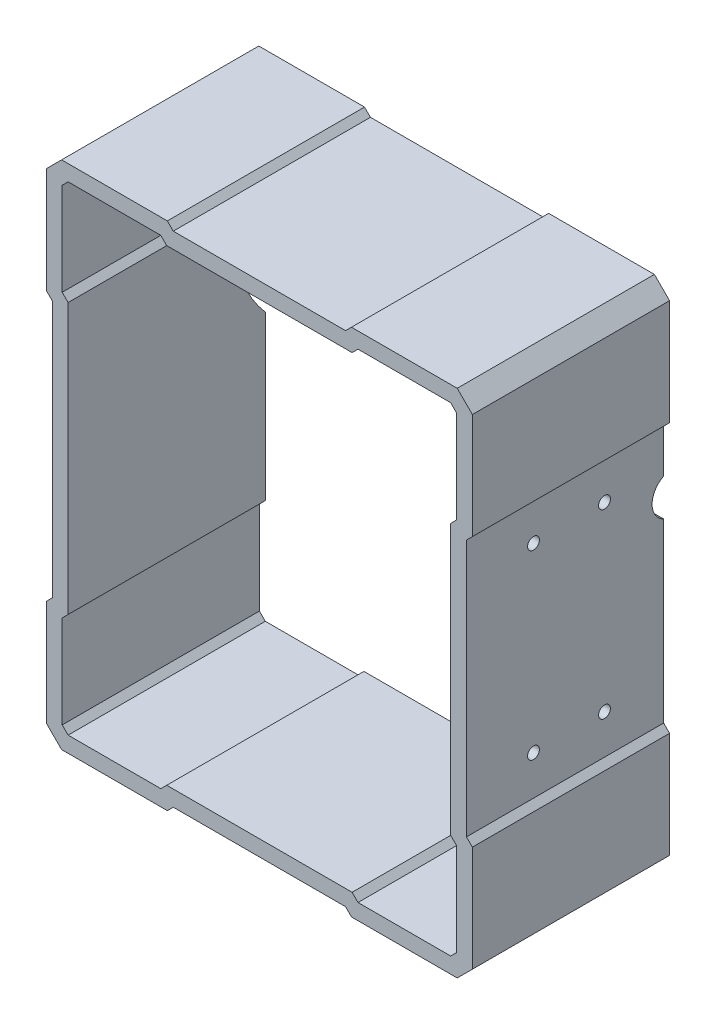
SolidWorks part; units mm, degrees
ref_plane "Front" through (0, 0, 0) normal (0, 0, 1) x (1, 0, 0)
ref_plane "Top" through (0, 0, 0) normal (0, 1, 0) x (1, 0, 0)
ref_plane "Right" through (0, 0, 0) normal (1, 0, 0) x (0, 0, -1)
sketch "草图1" plane through (0, 0, 0) normal (0, 0, 1) x (1, 0, 0)
  line L0 (25, 71.5) -> (23.5, 70) construction
  line L1 (23.5, 65.5) -> (25, 65.5) construction
  line L2 (25, 65.5) -> (43.5, 65.5) construction
  line L3 (43.5, 65.5) -> (43.5, 46.5) construction
  line L4 (50, 46.5) -> (50, 70) construction
  line L5 (50, 70) -> (48.5, 71.5) construction
  line L6 (48.5, 71.5) -> (25, 71.5) construction
  line L7 (23.5, 70) -> (-23.5, 70) construction
  line L8 (-23.5, 65.5) -> (23.5, 65.5) construction
  line L9 (-23.5, 70) -> (-25, 71.5) construction
  line L10 (-25, 65.5) -> (-23.5, 65.5) construction
  line L11 (-48.5, 71.5) -> (-50, 70) construction
  line L12 (-50, 70) -> (-50, 46.5) construction
  line L13 (-43.5, 46.5) -> (-43.5, 65.5) construction
  line L14 (-43.5, 65.5) -> (-25, 65.5) construction
  line L15 (-25, 71.5) -> (-48.5, 71.5) construction
  line L16 (-43.5, -23.5) -> (-43.5, -2.7997) construction
  line L17 (-43.5, 2.7997) -> (-43.5, 45) construction
  line L18 (-48.5, 45) -> (-48.5, -23.5) construction
  line L19 (-50, 46.5) -> (-48.5, 45) construction
  line L20 (-43.5, 45) -> (-43.5, 46.5) construction
  line L21 (-48.5, -23.5) -> (-50, -25) construction
  line L22 (-43.5, -25) -> (-43.5, -23.5) construction
  line L23 (-50, -25) -> (-50, -31.8) construction
  line L24 (-50, -31.8) -> (-43.5, -31.8) construction
  line L25 (-43.5, -31.8) -> (-43.5, -25) construction
  line L26 (-50, -31.8) -> (-50, -38.2) construction
  line L27 (-50, -38.2) -> (-43.5, -38.2) construction
  line L28 (-43.5, -38.2) -> (-43.5, -31.8) construction
  line L29 (-43.5, -31.8) -> (-50, -31.8) construction
  line L30 (-50, -48.5) -> (-48.5, -50) construction
  line L31 (-48.5, -50) -> (-38.2, -50) construction
  line L32 (-38.2, -50) -> (-38.2, -43.1) construction
  line L33 (-38.2, -43.1) -> (-43.5, -43.1) construction
  line L34 (-43.5, -43.1) -> (-43.5, -38.2) construction
  line L35 (-43.5, -38.2) -> (-50, -38.2) construction
  line L36 (-50, -38.2) -> (-50, -48.5) construction
  line L37 (-38.2, -50) -> (-31.8, -50) construction
  line L38 (-31.8, -50) -> (-31.8, -43.1) construction
  line L39 (-31.8, -43.1) -> (-38.2, -43.1) construction
  line L40 (-38.2, -43.1) -> (-38.2, -50) construction
  line L41 (-25, -43.1) -> (-31.8, -43.1) construction
  line L42 (-31.8, -43.1) -> (-31.8, -50) construction
  line L43 (-31.8, -50) -> (-25, -50) construction
  line L44 (-25, -50) -> (-23.5, -48.5) construction
  line L45 (-23.5, -43.1) -> (-25, -43.1) construction
  line L46 (23.5, -48.5) -> (25, -50) construction
  line L47 (25, -43.1) -> (23.5, -43.1) construction
  line L48 (23.5, -43.1) -> (6.5175, -43.1) construction
  line L49 (-6.5175, -43.1) -> (-23.5, -43.1) construction
  line L50 (-23.5, -48.5) -> (23.5, -48.5) construction
  line L51 (25, -50) -> (31.8, -50) construction
  line L52 (31.8, -50) -> (31.8, -43.1) construction
  line L53 (31.8, -43.1) -> (25, -43.1) construction
  line L54 (31.8, -50) -> (38.2, -50) construction
  line L55 (38.2, -50) -> (38.2, -43.1) construction
  line L56 (38.2, -43.1) -> (31.8, -43.1) construction
  line L57 (31.8, -43.1) -> (31.8, -50) construction
  line L58 (43.5, -38.2) -> (43.5, -43.1) construction
  line L59 (43.5, -43.1) -> (38.2, -43.1) construction
  line L60 (38.2, -43.1) -> (38.2, -50) construction
  line L61 (38.2, -50) -> (48.5, -50) construction
  line L62 (48.5, -50) -> (50, -48.5) construction
  line L63 (50, -48.5) -> (50, -38.2) construction
  line L64 (50, -38.2) -> (43.5, -38.2) construction
  line L65 (50, -38.2) -> (50, -31.8) construction
  line L66 (50, -31.8) -> (43.5, -31.8) construction
  line L67 (43.5, -31.8) -> (43.5, -38.2) construction
  line L68 (43.5, -38.2) -> (50, -38.2) construction
  line L69 (43.5, -25) -> (43.5, -31.8) construction
  line L70 (43.5, -31.8) -> (50, -31.8) construction
  line L71 (50, -31.8) -> (50, -25) construction
  line L72 (43.5, -23.5) -> (43.5, -25) construction
  line L73 (50, -25) -> (48.5, -23.5) construction
  line L74 (43.5, 46.5) -> (43.5, 45) construction
  line L75 (48.5, 45) -> (50, 46.5) construction
  line L76 (43.5, 45) -> (43.5, 2.7997) construction
  line L77 (43.5, -2.7997) -> (43.5, -23.5) construction
  line L78 (48.5, -23.5) -> (48.5, 45) construction
  line L79 (25, 71.5) -> (23.5, 70)
  line L80 (23.5, 65.5) -> (25, 65.5) construction
  line L81 (25, 65.5) -> (43.5, 65.5) construction
  line L82 (43.5, 65.5) -> (43.5, 46.5) construction
  line L83 (50, 46.5) -> (50, 70)
  line L84 (50, 70) -> (48.5, 71.5)
  line L85 (48.5, 71.5) -> (25, 71.5)
  line L86 (23.5, 70) -> (-23.5, 70)
  line L87 (-23.5, 65.5) -> (23.5, 65.5) construction
  line L88 (-23.5, 70) -> (-25, 71.5)
  line L89 (-25, 65.5) -> (-23.5, 65.5) construction
  line L90 (-48.5, 71.5) -> (-50, 70)
  line L91 (-50, 70) -> (-50, 46.5)
  line L92 (-43.5, 46.5) -> (-43.5, 65.5) construction
  line L93 (-43.5, 65.5) -> (-25, 65.5) construction
  line L94 (-25, 71.5) -> (-48.5, 71.5)
  line L95 (-43.5, -23.5) -> (-43.5, -2.7997) construction
  line L96 (-43.5, 2.7997) -> (-43.5, 45) construction
  line L97 (-48.5, 45) -> (-48.5, -23.5)
  line L98 (-50, 46.5) -> (-48.5, 45)
  line L99 (-43.5, 45) -> (-43.5, 46.5) construction
  line L100 (-48.5, -23.5) -> (-50, -25)
  line L101 (-43.5, -25) -> (-43.5, -23.5) construction
  line L102 (-50, -25) -> (-50, -31.8)
  line L103 (-50, -31.8) -> (-43.5, -31.8) construction
  line L104 (-43.5, -31.8) -> (-43.5, -25) construction
  line L105 (-50, -31.8) -> (-50, -38.2)
  line L106 (-50, -38.2) -> (-43.5, -38.2) construction
  line L107 (-43.5, -38.2) -> (-43.5, -31.8) construction
  line L108 (-43.5, -31.8) -> (-50, -31.8) construction
  line L109 (-50, -48.5) -> (-48.5, -50)
  line L110 (-48.5, -50) -> (-38.2, -50)
  line L111 (-38.2, -50) -> (-38.2, -43.1) construction
  line L112 (-38.2, -43.1) -> (-43.5, -43.1) construction
  line L113 (-43.5, -43.1) -> (-43.5, -38.2) construction
  line L114 (-43.5, -38.2) -> (-50, -38.2) construction
  line L115 (-50, -38.2) -> (-50, -48.5)
  line L116 (-38.2, -50) -> (-31.8, -50)
  line L117 (-31.8, -50) -> (-31.8, -43.1) construction
  line L118 (-31.8, -43.1) -> (-38.2, -43.1) construction
  line L119 (-38.2, -43.1) -> (-38.2, -50) construction
  line L120 (-25, -43.1) -> (-31.8, -43.1) construction
  line L121 (-31.8, -43.1) -> (-31.8, -50) construction
  line L122 (-31.8, -50) -> (-25, -50)
  line L123 (-25, -50) -> (-23.5, -48.5)
  line L124 (-23.5, -43.1) -> (-25, -43.1) construction
  line L125 (23.5, -48.5) -> (25, -50)
  line L126 (25, -43.1) -> (23.5, -43.1) construction
  line L127 (23.5, -43.1) -> (6.5175, -43.1) construction
  line L128 (-6.5175, -43.1) -> (-23.5, -43.1) construction
  line L129 (-23.5, -48.5) -> (23.5, -48.5)
  line L130 (25, -50) -> (31.8, -50)
  line L131 (31.8, -50) -> (31.8, -43.1) construction
  line L132 (31.8, -43.1) -> (25, -43.1) construction
  line L133 (31.8, -50) -> (38.2, -50)
  line L134 (38.2, -50) -> (38.2, -43.1) construction
  line L135 (38.2, -43.1) -> (31.8, -43.1) construction
  line L136 (31.8, -43.1) -> (31.8, -50) construction
  line L137 (43.5, -38.2) -> (43.5, -43.1) construction
  line L138 (43.5, -43.1) -> (38.2, -43.1) construction
  line L139 (38.2, -43.1) -> (38.2, -50) construction
  line L140 (38.2, -50) -> (48.5, -50)
  line L141 (48.5, -50) -> (50, -48.5)
  line L142 (50, -48.5) -> (50, -38.2)
  line L143 (50, -38.2) -> (43.5, -38.2) construction
  line L144 (50, -38.2) -> (50, -31.8)
  line L145 (50, -31.8) -> (43.5, -31.8) construction
  line L146 (43.5, -31.8) -> (43.5, -38.2) construction
  line L147 (43.5, -38.2) -> (50, -38.2) construction
  line L148 (43.5, -25) -> (43.5, -31.8) construction
  line L149 (43.5, -31.8) -> (50, -31.8) construction
  line L150 (50, -31.8) -> (50, -25)
  line L151 (43.5, -23.5) -> (43.5, -25) construction
  line L152 (50, -25) -> (48.5, -23.5)
  line L153 (43.5, 46.5) -> (43.5, 45) construction
  line L154 (48.5, 45) -> (50, 46.5)
  line L155 (43.5, 45) -> (43.5, 2.7997) construction
  line L156 (43.5, -2.7997) -> (43.5, -23.5) construction
  line L157 (48.5, -23.5) -> (48.5, 45)
  line L158 (54, -31.8) -> (54, -23.3431)
  line L159 (54, -23.3431) -> (52.5, -21.8431)
  line L160 (52.5, -21.8431) -> (52.5, 43.3431)
  line L161 (52.5, 43.3431) -> (54, 44.8431)
  line L162 (54, 44.8431) -> (54, 71.6569)
  line L163 (54, 71.6569) -> (50.1569, 75.5)
  line L164 (50.1569, 75.5) -> (23.3431, 75.5)
  line L165 (23.3431, 75.5) -> (21.8431, 74)
  line L166 (21.8431, 74) -> (-21.8431, 74)
  line L167 (-21.8431, 74) -> (-23.3431, 75.5)
  line L168 (-23.3431, 75.5) -> (-50.1569, 75.5)
  line L169 (-50.1569, 75.5) -> (-54, 71.6569)
  line L170 (-54, 71.6569) -> (-54, 44.8431)
  line L171 (-54, 44.8431) -> (-52.5, 43.3431)
  line L172 (-52.5, 43.3431) -> (-52.5, -21.8431)
  line L173 (-52.5, -21.8431) -> (-54, -23.3431)
  line L174 (-54, -23.3431) -> (-54, -31.8)
  line L175 (54, -38.2) -> (54, -31.8)
  line L176 (38.2, -54) -> (50.1569, -54)
  line L177 (50.1569, -54) -> (54, -50.1569)
  line L178 (54, -50.1569) -> (54, -38.2)
  line L179 (31.8, -54) -> (38.2, -54)
  line L180 (-31.8, -54) -> (-23.3431, -54)
  line L181 (-23.3431, -54) -> (-21.8431, -52.5)
  line L182 (-21.8431, -52.5) -> (21.8431, -52.5)
  line L183 (21.8431, -52.5) -> (23.3431, -54)
  line L184 (23.3431, -54) -> (31.8, -54)
  line L185 (-38.2, -54) -> (-31.8, -54)
  line L186 (-54, -38.2) -> (-54, -50.1569)
  line L187 (-54, -50.1569) -> (-50.1569, -54)
  line L188 (-50.1569, -54) -> (-38.2, -54)
  line L189 (-54, -31.8) -> (-54, -38.2)
  arc A0 (-43.5, 2.7997) -> (-43.5, -2.7997) centre (0, 0) ccw construction
  arc A1 (-6.5175, -43.1) -> (6.5175, -43.1) centre (0, 0) ccw construction
  arc A2 (43.5, -2.7997) -> (43.5, 2.7997) centre (0, 0) ccw construction
  arc A3 (-43.5, 2.7997) -> (-43.5, -2.7997) centre (0, 0) ccw construction
  arc A4 (-6.5175, -43.1) -> (6.5175, -43.1) centre (0, 0) ccw construction
  arc A5 (43.5, -2.7997) -> (43.5, 2.7997) centre (0, 0) ccw construction
  dimension "D1" = 4
extrude "凸台-拉伸1" add sketch "草图1" along normal mid plane 20
sketch "草图2" plane through (-52.5, 0, 0) normal (-1, 0, 0) x (0, 0, 1)
  line L0 (-10, 43.3431) -> (-10, -21.8431) construction
  line L1 (-10, 43.3431) -> (-10, 17.8909)
  line L2 (-10, 71.6569) -> (-10, 44.8431) construction
  line L3 (-10, 62.1091) -> (-10, 44.8431)
  line L4 (-10, 43.3431) -> (-10, 44.8431)
  arc A0 (-1.7971, 38.2166) -> (-1.7971, 41.7834) centre (-35.5, 40) ccw construction
  arc A1 (-17.1041, 11.7042) -> (-1.7971, 38.2166) centre (-35.5, 40) ccw construction
  arc A2 (-1.7971, 41.7834) -> (-17.1041, 68.2958) centre (-35.5, 40) ccw construction
  arc A3 (-1.7971, 38.2166) -> (-1.7971, 41.7834) centre (-35.5, 40) ccw
  arc A4 (-10, 17.8909) -> (-1.7971, 38.2166) centre (-35.5, 40) ccw
  arc A5 (-1.7971, 41.7834) -> (-10, 62.1091) centre (-35.5, 40) ccw
extrude "切除-拉伸1" cut sketch "草图2" along normal mid plane 10
sketch "草图3" plane through (52.5, 0, 0) normal (1, 0, 0) x (0, 0, -1)
  line L0 (10, -21.8431) -> (10, 43.3431) construction
  line L1 (10, 22.9681) -> (10, 32.3847)
  arc A0 (13.1086, 32.8672) -> (17.0655, 25.4253) centre (12.3226, 27.6764) ccw construction
  arc A1 (10, 32.3847) -> (10, 22.9681) centre (12.3226, 27.6764) ccw
extrude "切除-拉伸2" cut sketch "草图3" against normal blind 20 contours A1 L1
sketch "草图4" plane through (0, 0, 10) normal (0, 0, 1) x (1, 0, 0)
  line L24 (54, -50.1569) -> (54, -23.3431)
  line L25 (54, -23.3431) -> (52.5, -21.8431)
  line L26 (52.5, -21.8431) -> (52.5, 43.3431)
  line L27 (52.5, 43.3431) -> (54, 44.8431)
  line L28 (54, 44.8431) -> (54, 71.6569)
  line L29 (54, 71.6569) -> (50.1569, 75.5)
  line L30 (50.1569, 75.5) -> (23.3431, 75.5)
  line L31 (23.3431, 75.5) -> (21.8431, 74)
  line L32 (21.8431, 74) -> (-21.8431, 74)
  line L33 (-21.8431, 74) -> (-23.3431, 75.5)
  line L34 (-23.3431, 75.5) -> (-50.1569, 75.5)
  line L35 (-50.1569, 75.5) -> (-54, 71.6569)
  line L36 (-54, 71.6569) -> (-54, 44.8431)
  line L37 (-54, 44.8431) -> (-52.5, 43.3431)
  line L38 (-52.5, 43.3431) -> (-52.5, -21.8431)
  line L39 (-52.5, -21.8431) -> (-54, -23.3431)
  line L40 (-54, -23.3431) -> (-54, -50.1569)
  line L41 (-54, -50.1569) -> (-50.1569, -54)
  line L42 (-50.1569, -54) -> (-23.3431, -54)
  line L43 (-23.3431, -54) -> (-21.8431, -52.5)
  line L44 (-21.8431, -52.5) -> (21.8431, -52.5)
  line L45 (21.8431, -52.5) -> (23.3431, -54)
  line L46 (23.3431, -54) -> (50.1569, -54)
  line L47 (50.1569, -54) -> (54, -50.1569)
  line L48 (54, -50.1569) -> (54, -23.3431)
  line L49 (54, -23.3431) -> (52.5, -21.8431)
  line L50 (52.5, -21.8431) -> (52.5, 43.3431)
  line L51 (52.5, 43.3431) -> (54, 44.8431)
  line L52 (54, 44.8431) -> (54, 71.6569)
  line L53 (54, 71.6569) -> (50.1569, 75.5)
  line L54 (50.1569, 75.5) -> (23.3431, 75.5)
  line L55 (23.3431, 75.5) -> (21.8431, 74)
  line L56 (21.8431, 74) -> (-21.8431, 74)
  line L57 (-21.8431, 74) -> (-23.3431, 75.5)
  line L58 (-23.3431, 75.5) -> (-50.1569, 75.5)
  line L59 (-50.1569, 75.5) -> (-54, 71.6569)
  line L60 (-54, 71.6569) -> (-54, 44.8431)
  line L61 (-54, 44.8431) -> (-52.5, 43.3431)
  line L62 (-52.5, 43.3431) -> (-52.5, -21.8431)
  line L63 (-52.5, -21.8431) -> (-54, -23.3431)
  line L64 (-54, -23.3431) -> (-54, -50.1569)
  line L65 (-54, -50.1569) -> (-50.1569, -54)
  line L66 (-50.1569, -54) -> (-23.3431, -54)
  line L67 (-23.3431, -54) -> (-21.8431, -52.5)
  line L68 (-21.8431, -52.5) -> (21.8431, -52.5)
  line L69 (21.8431, -52.5) -> (23.3431, -54)
  line L70 (23.3431, -54) -> (50.1569, -54)
  line L71 (50.1569, -54) -> (54, -50.1569)
  line M49 (23.5, 70) -> (25, 71.5)
  line M50 (25, 71.5) -> (48.5, 71.5)
  line M51 (48.5, 71.5) -> (50, 70)
  line M52 (50, 70) -> (50, 46.5)
  line M53 (50, 46.5) -> (48.5, 45)
  line M54 (48.5, 45) -> (48.5, -23.5)
  line M55 (48.5, -23.5) -> (50, -25)
  line M56 (50, -25) -> (50, -48.5)
  line M57 (50, -48.5) -> (48.5, -50)
  line M58 (48.5, -50) -> (25, -50)
  line M59 (25, -50) -> (23.5, -48.5)
  line M60 (23.5, -48.5) -> (-23.5, -48.5)
  line M61 (-23.5, -48.5) -> (-25, -50)
  line M62 (-25, -50) -> (-48.5, -50)
  line M63 (-48.5, -50) -> (-50, -48.5)
  line M64 (-50, -48.5) -> (-50, -25)
  line M65 (-50, -25) -> (-48.5, -23.5)
  line M66 (-48.5, -23.5) -> (-48.5, 45)
  line M67 (-48.5, 45) -> (-50, 46.5)
  line M68 (-50, 46.5) -> (-50, 70)
  line M69 (-50, 70) -> (-48.5, 71.5)
  line M70 (-48.5, 71.5) -> (-25, 71.5)
  line M71 (-25, 71.5) -> (-23.5, 70)
  line M72 (-23.5, 70) -> (23.5, 70)
  dimension "D1" = 0
extrude "凸台-拉伸2" add sketch "草图4" along normal blind 30 contours M49 M72 M71 M70 M69 M68 M67 M66 M65 M64 M63 M62 M61 M60 M59 M58 M57 M56 M55 M54 M53 M52 M51 M50 | L54 L55 L56 L57 L58 L59 L60 L61 L62 L63 L64 L65 L66 L67 L68 L69 L70 L71 L48 L49 L50 L51 L52 L53 region at (0, 10.75, 10)
sketch "草图5" plane through (48.5, 0, 0) normal (-1, 0, 0) x (0, 0, 1)
  circle A0 centre (5, -11.8684) radius 1.5 construction
  circle A1 centre (23, -11.8684) radius 1.5 construction
  circle A2 centre (5, 34.1316) radius 1.5 construction
  circle A3 centre (23, 34.1316) radius 1.5 construction
  circle A4 centre (5, -11.8684) radius 1.5
  circle A5 centre (23, -11.8684) radius 1.5
  circle A6 centre (5, 34.1316) radius 1.5
  circle A7 centre (23, 34.1316) radius 1.5
extrude "切除-拉伸3" cut sketch "草图5" against normal blind 10
